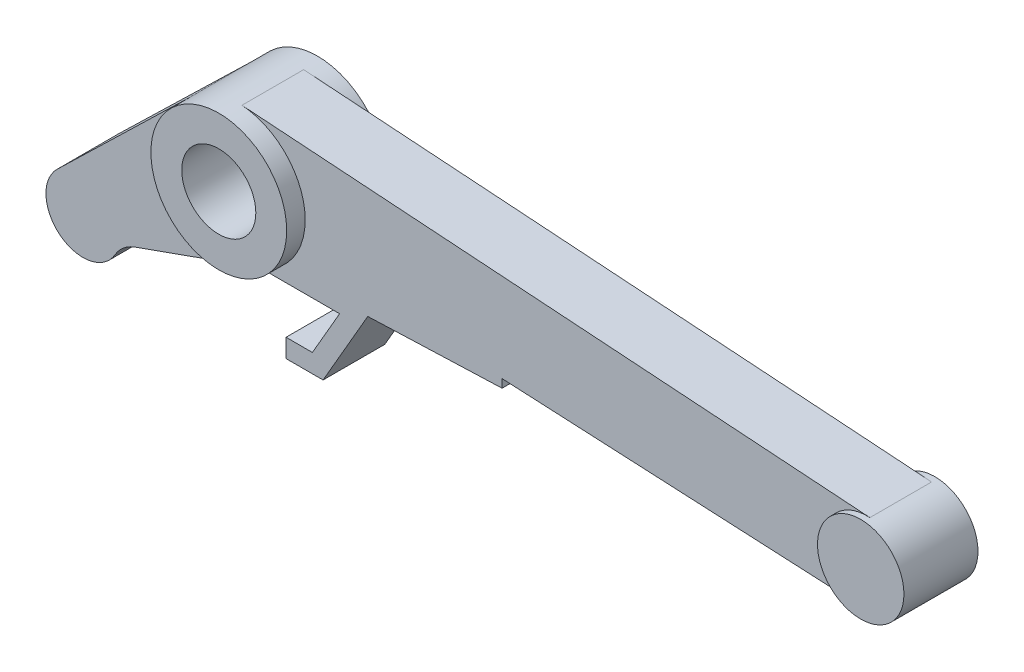
SolidWorks part; units mm, degrees
material "Wrought Stainless Steel"
ref_plane "Front Plane" through (0, 0, 0) normal (0, 0, 1) x (1, 0, 0)
ref_plane "Top Plane" through (0, 0, 0) normal (0, 1, 0) x (1, 0, 0)
ref_plane "Right Plane" through (0, 0, 0) normal (1, 0, 0) x (0, 0, -1)
sketch "Sketch1" plane through (0, 0, 0) normal (0, 0, 1) x (1, 0, 0)
  line L0 (-319.8394, 0) -> (15672.131, 0) construction
  line L1 (0, -319.8394) -> (0, 15672.131) construction
  circle A0 centre (0, 0) radius 11
  circle A1 centre (0, 0) radius 6
  dimension "D1" = 22
  dimension "D2" = 12
extrude "Boss-Extrude1" add sketch "Sketch1" along normal mid plane 16
sketch "Sketch2" plane through (0, 0, 0) normal (0, 0, 1) x (1, 0, 0)
  line L0 (-7.6556, 7.8989) -> (-29.1758, -12.9585)
  line L1 (-25, -17.267) -> (-9.051, -6.2514) construction
  line L2 (-16.6185, -17.607) -> (3.6958, -10.3606)
  line L3 (3.6958, -10.3606) -> (16.5766, -10.3606)
  line L4 (16.5766, -10.3606) -> (12.166, -18)
  line L5 (12.166, -18) -> (7.898, -18)
  line L6 (7.898, -18) -> (7.898, -21)
  line L7 (7.898, -21) -> (13.898, -21)
  line L8 (13.898, -21) -> (21.1382, -8.4597)
  line L9 (21.1382, -8.4597) -> (42.898, -7.6519)
  line L10 (42.898, -7.6519) -> (42.898, -6.3029)
  line L11 (42.898, -6.3029) -> (98.5, -9.0622)
  line L12 (11, 0) -> (49000, 0) construction
  line L13 (-1000, 0) -> (-5.1321, 0) construction
  line L14 (102.4799, 3.9835) -> (0.7541, 10.9741)
  circle A0 centre (102, -3) radius 7
  circle A1 centre (0, 0) radius 11 construction
  arc A2 (-29.1758, -12.9585) -> (-19.8013, -20.2626) centre (-25, -17.267) ccw
  arc A3 (-19.8013, -20.2626) -> (-16.6185, -17.607) centre (-14.6026, -23.2582) cw
  arc A4 (0.7541, 10.9741) -> (-7.6556, 7.8989) centre (0, 0) ccw
  point P8 (-28.6877, -22)
  dimension "D1" = 22
  dimension "D3" = 6
  dimension "D4" = 6
  dimension "D5" = 15
  dimension "D9" = 3
  dimension "D10" = 14
  dimension "D2" = 25
  dimension "D6" = 6
  dimension "D7" = 3
  dimension "D8" = 3
  dimension "D11" = 35
  dimension "D12" = 21
  dimension "D13" = 102
extrude "Boss-Extrude2" add sketch "Sketch2" along normal mid plane 12 separate body contours A0 region at (102, -3, 0)
extrude "Boss-Extrude3" add sketch "Sketch2<3>" along normal mid plane 10 contours L14 A4 L0 A2 A3 L2 L3 L4 L5 L6 L7 L8 L9 L10 L11 A0 region at (28.5155, -2.4355, 0)
sketch "Sketch2<3>" plane through (0, 0, 0) normal (0, 0, 1) x (1, 0, 0) same geometry as "Sketch2"
sketch "Sketch3" plane through (0, 0, 0) normal (0, 0, 1) x (1, 0, 0)
  circle A0 centre (0, 0) radius 6 construction
  circle A1 centre (0, 0) radius 6
extrude "Cut-Extrude1" cut sketch "Sketch3" against normal through all both and the other way through all
